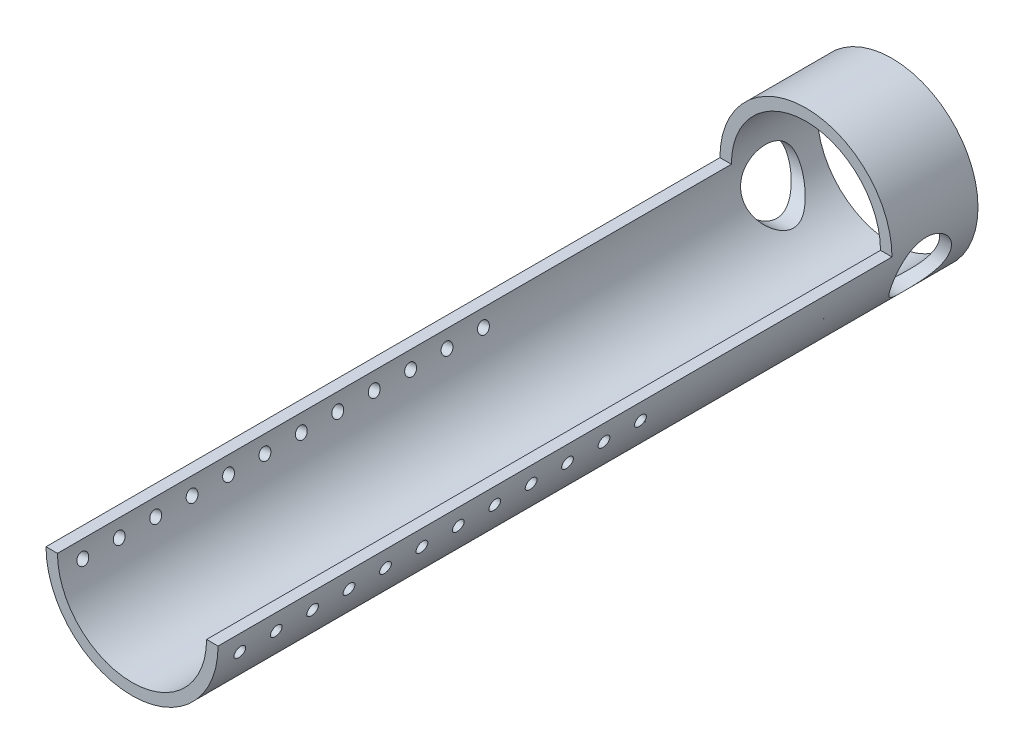
SolidWorks part; units mm, degrees
note: '?' marks a value the reader was unsure of.
ref_plane "Front" through (0, 0, 0) normal (0, 0, 1) x (1, 0, 0)
ref_plane "Top" through (0, 0, 0) normal (0, 1, 0) x (1, 0, 0)
ref_plane "Right" through (0, 0, 0) normal (1, 0, 0) x (0, 0, -1)
sketch "Sketch1" plane through (0, 0, 0) normal (0, 0, 1) x (1, 0, 0)
  circle A0 centre (0, 0) radius 30
  circle A1 centre (0, 0) radius 26
  dimension "D1" = 60
  dimension "D2" = 4
extrude "Boss-Extrude1" add sketch "Sketch1" along normal mid plane 265
sketch "Sketch3" plane through (0, 0, 132.5) normal (0, 0, 1) x (1, 0, 0)
  line L0 (-30, 0) -> (30, 0)
  line L1 (-30, 0) -> (-30, 30)
  line L2 (30, 0) -> (30, 30)
  line L3 (-30, 30) -> (30, 30)
  line L4 (50, 0) -> (-50, 0) construction
  circle A0 centre (0, 0) radius 30 construction
extrude "Cut-Extrude1" cut sketch "Sketch3" against normal blind 235
sketch "Sketch4" plane through (0, 0, 0) normal (1, 0, 0) x (0, 0, -1)
  line L0 (-132.5, 0) -> (-132.5, -30) construction
  line L1 (102.5, 0) -> (-132.5, 0) construction
  point P0 (-122.34, -6.35)
  dimension "D1" = 10.16
  dimension "D2" = 6.35
ref_axis "Axis1" through (0, -6.35, 122.34) along (1, 0, 0)?
hole_wizard "#10-32 Tapped Hole1" positions "3DSketch3" profile "Sketch7" tap size "#10-32" standard "ANSI Inch" end condition through all
sketch3d "3DSketch3"
  line L0 (30, 0, -102.5) -> (30, 0, 132.5) construction
  point P0 (29.328, -6.3143, 124.246)
  dimension "D2" = 10.414
  dimension "D1" = 6.35
sketch "Sketch7" plane through (29.328, -6.3143, 124.246) normal (0, 0, 1) x (0.2105, 0.9776, 0)
  line L0 (0, 0) -> (0, 65.6423)
  line L1 (0, 65.6423) -> (2.0193, 65.6423)
  line L2 (2.0193, 65.6423) -> (2.0193, 0)
  line L5 (2.0193, 0) -> (0, 0)
  line L11 (0, -6.35) -> (0, 107.95) construction
  dimension "Thru Tap Drill Dia." = 4.0386
  dimension "Thru Tap Drill Depth" = 65.6423
cosmetic thread "Hole Thread1" parameters "D2"=4.826
pattern_linear "LPattern1" count 12 spacing 12.7 along (0, 0, -1) of "#10-32 Tapped Hole1"
cosmetic thread "Hole Thread2" parameters "D2"=4.826
cosmetic thread "Hole Thread3" parameters "D2"=4.826
cosmetic thread "Hole Thread4" parameters "D2"=4.826
cosmetic thread "Hole Thread5" parameters "D2"=4.826
cosmetic thread "Hole Thread6" parameters "D2"=4.826
cosmetic thread "Hole Thread7" parameters "D2"=4.826
cosmetic thread "Hole Thread8" parameters "D2"=4.826
cosmetic thread "Hole Thread9" parameters "D2"=4.826
cosmetic thread "Hole Thread10" parameters "D2"=4.826
cosmetic thread "Hole Thread11" parameters "D2"=4.826
cosmetic thread "Hole Thread12" parameters "D2"=4.826
mirror "Mirror1" about plane through (0, 0, 0) normal (1, 0, 0) of "LPattern1", "#10-32 Tapped Hole1"
cosmetic thread "Hole Thread13" parameters "D2"=4.826
cosmetic thread "Hole Thread14" parameters "D2"=4.826
cosmetic thread "Hole Thread15" parameters "D2"=4.826
cosmetic thread "Hole Thread16" parameters "D2"=4.826
cosmetic thread "Hole Thread17" parameters "D2"=4.826
cosmetic thread "Hole Thread18" parameters "D2"=4.826
cosmetic thread "Hole Thread19" parameters "D2"=4.826
cosmetic thread "Hole Thread20" parameters "D2"=4.826
cosmetic thread "Hole Thread21" parameters "D2"=4.826
cosmetic thread "Hole Thread22" parameters "D2"=4.826
cosmetic thread "Hole Thread23" parameters "D2"=4.826
cosmetic thread "Hole Thread24" parameters "D2"=4.826
sketch "Sketch8" plane through (0, 0, 0) normal (1, 0, 0) x (0, 0, -1)
  line L0 (50, 0) -> (-50, 0) construction
  line L1 (-132.5, -30) -> (132.5, -30) construction
  line L2 (124.5625, 0) -> (124.5625, -18.631) construction
  line L3 (132.5, -30) -> (132.5, 30) construction
  circle A0 centre (114.4025, -10.16) radius 10.16
  dimension "D1" = 20.32
  dimension "D2" = 7.9375
extrude "Cut-Extrude2" cut sketch "Sketch8" against normal through all both and the other way through all
hole_wizard "#10-32 Tapped Hole2" [suppressed] positions "3DSketch4" profile "Sketch10" tap size "#10-32" standard "ANSI Inch"
sketch3d "3DSketch4"
  line L0 (30, 0, -56.5) -> (30, 0, 86.5) construction
  point P0 (29.328, -6.3143, 78.246)
  dimension "D1" = 6.35
  dimension "D2" = 10.414
sketch "Sketch10" plane through (29.328, -6.3143, 78.246) normal (0, 0, 1) x (0.2105, 0.9776, 0)
  line L0 (0, 0) -> (0, 65.6423)
  line L1 (0, 65.6423) -> (2.0193, 65.6423)
  line L2 (2.0193, 65.6423) -> (2.0193, 0)
  line L5 (2.0193, 0) -> (0, 0)
  line L11 (0, -6.35) -> (0, 107.95) construction
  dimension "Thru Tap Drill Dia." = 4.0386
  dimension "Thru Tap Drill Depth" = 65.6423
cosmetic thread "Hole Thread25" [suppressed] parameters "D2"=4.826
pattern_linear "LPattern2" [suppressed] count 10 spacing 12.7
cosmetic thread "Hole Thread26" [suppressed] parameters "D2"=4.826
cosmetic thread "Hole Thread27" [suppressed] parameters "D2"=4.826
cosmetic thread "Hole Thread28" [suppressed] parameters "D2"=4.826
cosmetic thread "Hole Thread29" [suppressed] parameters "D2"=4.826
cosmetic thread "Hole Thread30" [suppressed] parameters "D2"=4.826
cosmetic thread "Hole Thread31" [suppressed] parameters "D2"=4.826
cosmetic thread "Hole Thread32" [suppressed] parameters "D2"=4.826
cosmetic thread "Hole Thread33" [suppressed] parameters "D2"=4.826
cosmetic thread "Hole Thread34" [suppressed] parameters "D2"=4.826
mirror "Mirror2" [suppressed] about plane through (0, 0, 0) normal (1, 0, 0)
cosmetic thread "Hole Thread35" [suppressed] parameters "D2"=4.826
cosmetic thread "Hole Thread36" [suppressed] parameters "D2"=4.826
cosmetic thread "Hole Thread37" [suppressed] parameters "D2"=4.826
cosmetic thread "Hole Thread38" [suppressed] parameters "D2"=4.826
cosmetic thread "Hole Thread39" [suppressed] parameters "D2"=4.826
cosmetic thread "Hole Thread40" [suppressed] parameters "D2"=4.826
cosmetic thread "Hole Thread41" [suppressed] parameters "D2"=4.826
cosmetic thread "Hole Thread42" [suppressed] parameters "D2"=4.826
cosmetic thread "Hole Thread43" [suppressed] parameters "D2"=4.826
cosmetic thread "Hole Thread44" [suppressed] parameters "D2"=4.826
sketch "Sketch11" [suppressed] plane through (0, 0, 0) normal (1, 0, 0) x (0, 0, -1)
  line L0 (78.5625, 3.9096) -> (78.5625, -22.4578) construction
  line L1 (86.5, -30) -> (86.5, 30) construction
  line L2 (50, 0) -> (-50, 0) construction
  circle A0 centre (68.4025, -10.16) radius 10.16
  dimension "D2" = 20.32
  dimension "D1" = 7.9375
extrude "Cut-Extrude3" [suppressed] cut sketch "Sketch11" against normal through all both and the other way through all
ref_point "Point1" [suppressed]
ref_point "Point2" [suppressed]
ref_point "Point3" [suppressed]
ref_plane "Plane1" [suppressed] through (27.3369, -5.8857, 0) normal (0.9776, -0.2105, 0) x (0, 0, -1)
ref_plane "Plane2" [suppressed] through (0, -0.0001, 0) normal (0.2105, 0.9776, 0) x (0.9776, -0.2105, 0)
